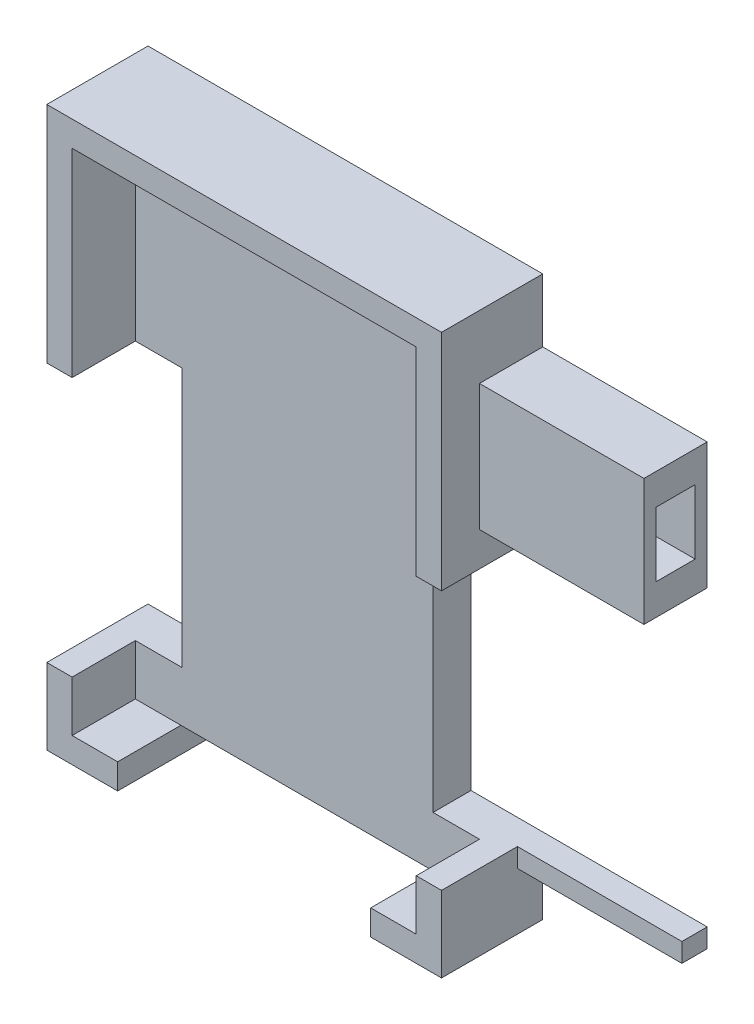
SolidWorks part; units mm, degrees
ref_plane "Front Plane" through (0, 0, 0) normal (0, 0, 1) x (1, 0, 0)
ref_plane "Top Plane" through (0, 0, 0) normal (0, 1, 0) x (1, 0, 0)
ref_plane "Right Plane" through (0, 0, 0) normal (1, 0, 0) x (0, 0, -1)
sketch "Sketch1" plane through (0, 0, 0) normal (0, 0, 1) x (1, 0, 0)
  line L0 (0, 125.6426) -> (0, -121.4419) construction
  line L1 (115.8733, 0) -> (-115.4548, 0) construction
  line L2 (15.6, 17.1) -> (28.6, 17.1)
  line L3 (-13.6, 20.1) -> (13.6, 20.1)
  line L4 (-13.6, 20.1) -> (-13.6, -20.1)
  line L5 (-13.6, -20.1) -> (13.6, -20.1)
  line L6 (13.6, 20.1) -> (13.6, -20.1)
  line L7 (-15.6, 22.1) -> (15.6, 22.1)
  line L8 (-15.6, 22.1) -> (-15.6, -22.1)
  line L9 (-15.6, -22.1) -> (15.6, -22.1)
  line L10 (15.6, 22.1) -> (15.6, -22.1)
  line L11 (28.6, 17.1) -> (28.6, 7.1)
  line L12 (28.6, 7.1) -> (15.6, 7.1)
  line L13 (11.43, 34.3394) -> (11.43, -39.7508) construction
  line L18 (-11.43, 31.8587) -> (-11.43, -35.1753) construction
  line L19 (-35.462, -16.1) -> (38.077, -16.1) construction
  line L20 (-9.93, -16.1) -> (-20.8868, -16.1)
  line L21 (9.93, 4.4) -> (20.8868, 4.4)
  line L22 (9.93, 4.4) -> (9.93, -16.1)
  line L23 (9.93, -16.1) -> (20.8868, -16.1)
  line L24 (20.8868, 4.4) -> (20.8868, -16.1)
  line L25 (-20.8868, 4.4) -> (-20.8868, -16.1)
  line L26 (-9.93, 4.4) -> (-20.8868, 4.4)
  line L27 (-9.93, 4.4) -> (-9.93, -16.1)
  line L28 (-10, -20.1) -> (-10, -22.1)
  line L29 (10, -20.1) -> (10, -22.1)
  line L30 (-35.1462, 12.1) -> (46.8082, 12.1) construction
  dimension "D1" = 31.2
  dimension "D2" = 2
  dimension "D3" = 27.2
  dimension "D4" = 40.2
  dimension "D5" = 22.86
  dimension "D6" = 4
  dimension "D7" = 1.5
  dimension "D8" = 20.5
  dimension "D9" = 10
  dimension "D10" = 10
  dimension "D11" = 5
  dimension "D12" = 13
  dimension "D13" = 28.6
  dimension "D14" = 28.2
extrude "Boss-Extrude1" add sketch "Sketch1" along normal blind 3 contours L26 L27 L20 L4 L5 L6 L23 L22 L21 L3 region at (0, 0.9335, 0)
extrude "Boss-Extrude2" add sketch "Sketch1<3>" along normal blind 5 contours L26 L4 L3 L6 L21 L10 L7 L8 | L5 L29 L9 L10 L23 L6 | L28 L5 L4 L20 L8 L9 region at (15.2413, 12.1, 0) region at (15.5179, -19.1, 0) region at (-14.6, -16.1821, 0)
sketch "Sketch1<3>" plane through (0, 0, 0) normal (0, 0, 1) x (1, 0, 0) same geometry as "Sketch1"
extrude "Boss-Extrude3" add sketch "Sketch1<4>" along normal blind 5 contours L12 L11 L2 L10 region at (22.1, 12.1, 0)
sketch "Sketch1<4>" plane through (0, 0, 0) normal (0, 0, 1) x (1, 0, 0) same geometry as "Sketch1"
sketch "Sketch2" plane through (28.6, 0, 0) normal (1, 0, 0) x (0, 0, -1)
  line L0 (0, 29.5595) -> (0, -33.1158) construction
  line L1 (-8.6556, 17.1) -> (3.1924, 17.1) construction
  line L2 (-5, 17.1) -> (0, 17.1) construction
  line L3 (-9.4008, 7.1) -> (5.047, 7.1) construction
  line L4 (-5, 7.1) -> (0, 7.1) construction
  line L5 (-2.5, 17.4146) -> (-2.5, 3.5219) construction
  line L6 (-7.7956, 12.1) -> (3.8426, 12.1) construction
  line L8 (-4.05, 14.65) -> (-0.95, 14.65)
  line L9 (-4.05, 14.65) -> (-4.05, 9.55)
  line L10 (-4.05, 9.55) -> (-0.95, 9.55)
  line L11 (-0.95, 14.65) -> (-0.95, 9.55)
  dimension "D1" = 2.5
  dimension "D2" = 5
  dimension "D3" = 5
  dimension "D4" = 3.1
  dimension "D5" = 5.1
extrude "Cut-Extrude1" cut sketch "Sketch2" against normal blind 6 contours L9 L8 L11 L10
extrude "Boss-Extrude4" add sketch "Sketch1<5>" along normal blind 8 contours L26 L4 L3 L6 L21 L10 L7 L8 | L28 L5 L4 L20 L8 L9 | L5 L29 L9 L10 L23 L6 region at (15.2413, 12.1, 0) region at (15.5179, -19.1, 0) region at (-14.6, -16.1821, 0)
sketch "Sketch1<5>" plane through (0, 0, 0) normal (0, 0, 1) x (1, 0, 0) same geometry as "Sketch1"
sketch "Sketch3" plane through (0, 0, 0) normal (0, 0, -1) x (-1, 0, 0)
  line L0 (-28.6, 7.1) -> (-15.6, 7.1) construction
  line L1 (-15.6, -16.1) -> (-28.6, -16.1)
  line L2 (-15.6, -16.1) -> (-15.6, -17.6)
  line L3 (-15.6, -17.6) -> (-28.6, -17.6)
  line L4 (-28.6, -16.1) -> (-28.6, -17.6)
  dimension "D1" = 1.5
extrude "Boss-Extrude5" add sketch "Sketch3" against normal blind 2
